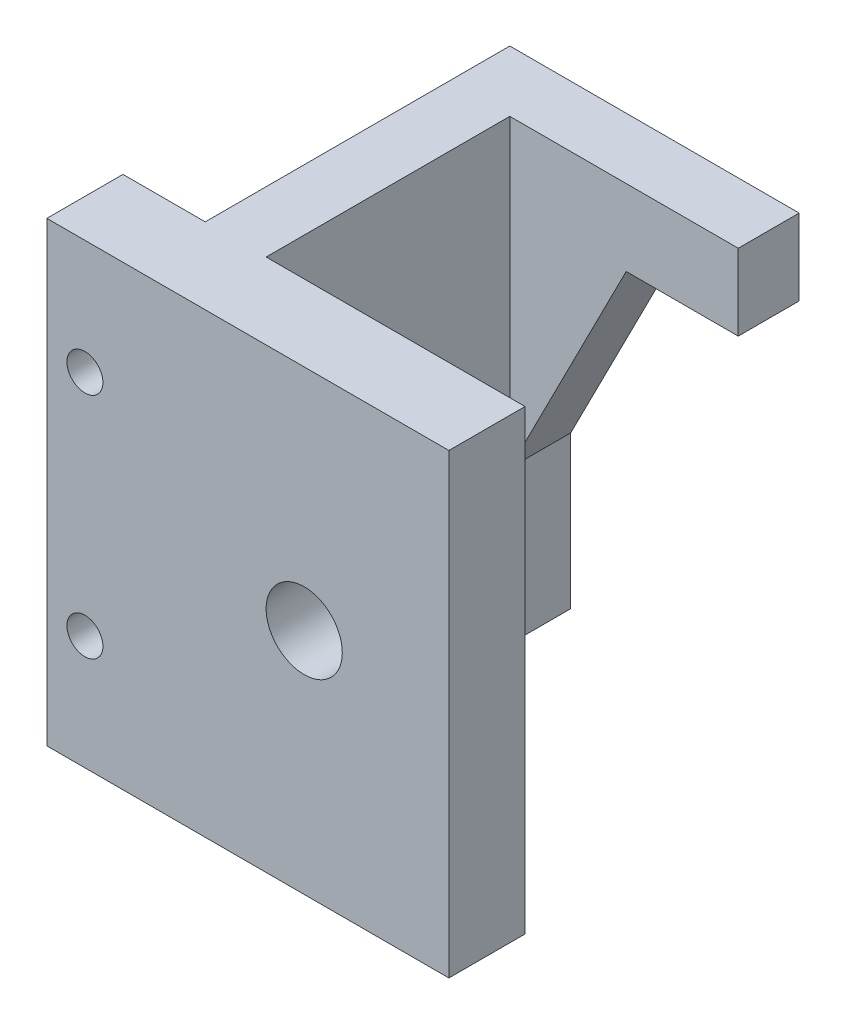
SolidWorks part; units mm, degrees
material "ABS"
ref_plane "Front Plane" through (0, 0, 0) normal (0, 0, 1) x (1, 0, 0)
ref_plane "Top Plane" through (0, 0, 0) normal (0, 1, 0) x (1, 0, 0)
ref_plane "Right Plane" through (0, 0, 0) normal (1, 0, 0) x (0, 0, -1)
sketch "Sketch2" plane through (0, 0, 0) normal (1, 0, 0) x (0, 0, -1)
  line L1 (-3.175, -19.05) -> (3.175, -19.05)
  line L2 (-3.175, -19.05) -> (-3.175, 19.05)
  line L3 (-3.175, 19.05) -> (3.175, 19.05)
  line L4 (3.175, -19.05) -> (3.175, 19.05)
  line L5 (-3.175, -19.05) -> (3.175, 19.05) construction
  line L6 (-3.175, 19.05) -> (3.175, -19.05) construction
  point P0 (0, 0)
  dimension "D1" = 38.1
  dimension "D2" = 6.35
extrude "Boss-Extrude1" add sketch "Sketch2" along normal blind 19.05
sketch "Sketch3" plane through (0, 0, 3.175) normal (0, 0, 1) x (1, 0, 0)
  line L0 (19.05, -19.05) -> (0, -19.05) construction
  line L1 (0, 19.05) -> (6.35, 19.05)
  line L2 (0, 19.05) -> (0, -19.05)
  line L3 (0, -19.05) -> (6.35, -19.05)
  line L4 (6.35, 19.05) -> (6.35, -19.05)
  line L5 (3.175, 19.05) -> (3.175, 9.525) construction
  line L6 (3.175, 9.525) -> (3.175, -9.525) construction
  line L7 (3.175, -9.525) -> (3.175, -19.05) construction
  circle A0 centre (3.175, 9.525) radius 1.5
  circle A1 centre (3.175, -9.525) radius 1.5
  dimension "D3" = 3
  dimension "D1" = 6.35
  dimension "D2" = 19.05
extrude "Cut-Extrude1" cut sketch "Sketch3" against normal through all contours A0 | A1 region at (3.175, 9.525, 3.175) region at (3.175, -9.525, 3.175)
sketch "Sketch4" plane through (0, 19.05, 0) normal (0, 1, 0) x (1, 0, 0)
  line L0 (6.858, -3.175) -> (6.858, 28.575)
  line L1 (19.05, -3.175) -> (0, -3.175) construction
  line L2 (0, 3.175) -> (0, -3.175) construction
  line L3 (6.858, 28.575) -> (11.938, 28.575)
  line L4 (11.938, 4.445) -> (30.988, 4.445) construction
  line L5 (11.938, 4.445) -> (11.938, 23.495) construction
  line L6 (11.938, 23.495) -> (30.988, 23.495) construction
  line L7 (30.988, 4.445) -> (30.988, 23.495) construction
  line L8 (11.938, 28.575) -> (11.938, 3.175)
  line L9 (19.05, 3.175) -> (0, 3.175) construction
  line L10 (19.05, 3.175) -> (33.528, 3.175)
  line L11 (33.528, 3.175) -> (33.528, -3.175)
  line L12 (33.528, -3.175) -> (19.05, -3.175)
  line L13 (19.05, -3.175) -> (6.858, -3.175)
  line L14 (19.05, 3.175) -> (11.938, 3.175)
  line L15 (11.938, 28.575) -> (21.463, 28.575)
  line L16 (21.463, 28.575) -> (21.463, 23.495)
  line L17 (21.463, 23.495) -> (11.938, 23.495)
  line M17 (0, -3.175) -> (19.05, -3.175)
  line M18 (19.05, -3.175) -> (19.05, 3.175)
  line M19 (19.05, 3.175) -> (0, 3.175)
  dimension "D1" = 6.858
  dimension "D2" = 19.05
  dimension "D3" = 5.08
  dimension "D4" = 1.27
  dimension "D5" = 2.54
  dimension "D6" = 5.08
  dimension "D7" = 9.525
extrude "Boss-Extrude2" add sketch "Sketch4" against normal up to surface (38.1 mm away) contours L12 L11 L10 M18 | L0 M17 M18 M19 | L8 L3 L0 M19 | L17 L16 L15 L8 region at (12.954, 19.05, 0) region at (9.398, 19.05, -15.875) region at (26.289, 19.05, 0) region at (16.7005, 19.05, -26.035) up to face at (9.525, -19.05, 0)
sketch "Sketch5" plane through (0, 0, 3.175) normal (0, 0, 1) x (1, 0, 0)
  line L0 (11.938, 19.05) -> (30.988, 19.05) construction
  circle A0 centre (21.463, 0) radius 3.175
  point P4 (21.463, 19.05)
  dimension "D1" = 6.35
extrude "Cut-Extrude2" cut sketch "Sketch5" against normal up to surface (6.35 mm away) up to face at (4.675, -9.525, -3.175)
sketch "Sketch6" plane through (0, 0, -28.575) normal (0, 0, -1) x (-1, 0, 0)
  line L0 (-6.858, -19.05) -> (-6.858, 19.05)
  line L1 (-6.858, 19.05) -> (-30.988, 19.05)
  line L2 (-33.528, 19.05) -> (-11.938, 19.05) construction
  line L3 (-30.988, 19.05) -> (-30.988, 12.7)
  line L4 (-30.988, 12.7) -> (-21.6445, 12.7)
  line L5 (-21.6445, 12.7) -> (-11.938, -6.35)
  line L6 (-11.938, -6.35) -> (-11.938, -19.05)
  line L7 (-11.938, -19.05) -> (-6.858, -19.05)
  line L8 (-33.528, -19.05) -> (-33.528, 19.05) construction
  line M8 (-21.463, 19.05) -> (-21.463, -19.05)
  line M9 (-21.463, -19.05) -> (-6.858, -19.05)
  dimension "D1" = 2.54
  dimension "D2" = 6.35
  dimension "D3" = 5.08
  dimension "D4" = 12.7
  dimension "D5" = 27
extrude "Cut-Extrude3" cut sketch "Sketch6" against normal up to surface (5.08 mm away) contours L6 L5 M8 M9 region at (17.3735, -7.3661, -28.575) up to face at (16.7005, 0, -23.495)
extrude "Boss-Extrude3" add sketch "Sketch6<3>" against normal up to surface (5.08 mm away) contours L4 L5 L1 L3 M8 region at (26.223, 15.8732, -28.575) up to face at (16.7005, 11.0235, -23.495)
sketch "Sketch6<3>" plane through (0, 0, -28.575) normal (0, 0, -1) x (-1, 0, 0) same geometry as "Sketch6"
